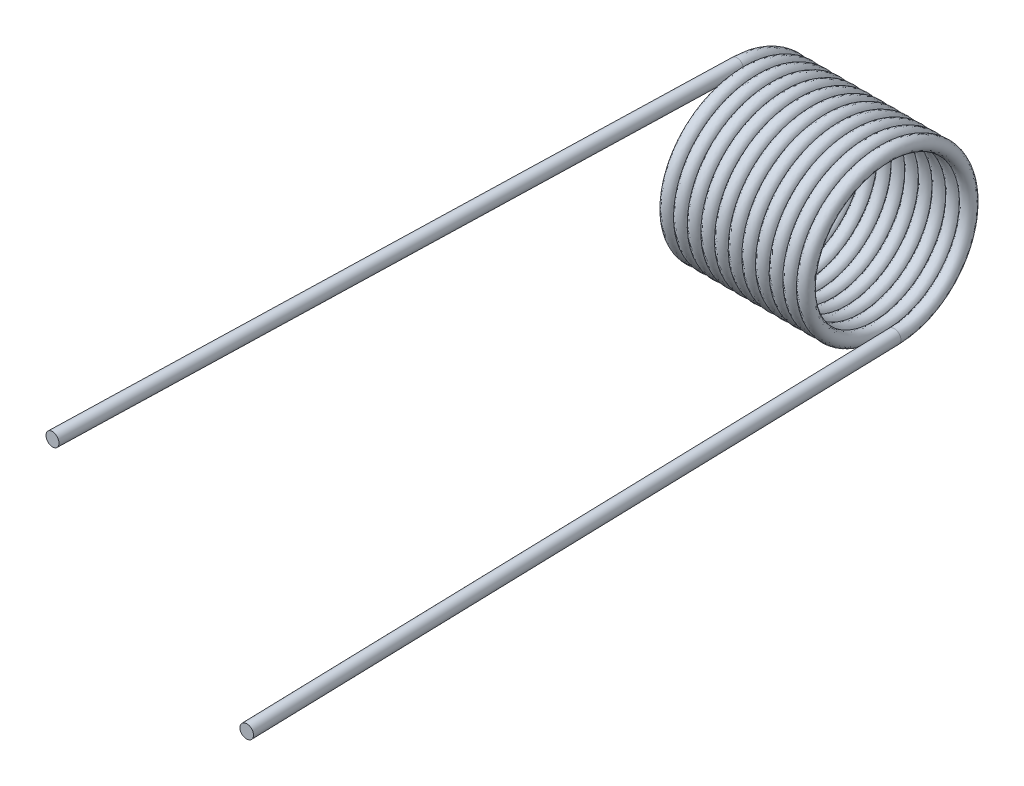
SolidWorks part; units mm, degrees
ref_plane "Front" through (0, 0, 0) normal (0, 0, 1) x (1, 0, 0)
ref_plane "Top" through (0, 0, 0) normal (0, 1, 0) x (1, 0, 0)
ref_plane "Right" through (0, 0, 0) normal (1, 0, 0) x (0, 0, -1)
sketch "Sketch1" plane through (0, 0, 0) normal (1, 0, 0) x (0, 0, -1)
  line L0 (0, 0) -> (0, -5.4356) construction
  line L1 (0, -5.4356) -> (0, -5.9436) construction
  line L2 (0, -5.9436) -> (0, -6.4516) construction
  circle A0 centre (0, 0) radius 5.4356 construction
  circle A1 centre (0, 0) radius 6.4516 construction
  circle A2 centre (0, 0) radius 5.9436
  circle A3 centre (0, -5.9436) radius 0.508 construction
  circle A4 centre (0, 0) radius 4.3561 construction
  dimension "Wire Dia" = 1.016
curve "Helix/Spiral1" pitch 1.0414 height 11.9761 radius 5.9436 left hand yes centre (0, 0, 0) axis (1, 0, 0) start towards (0, 1, 0)
ref_plane "Plane1" through (0, 5.9436, 0) normal (0.0279, 0, -0.9996) x (0.7745, 0.6323, 0.0216)
sketch "Sketch2" plane through (0, 5.9436, 0) normal (0.0279, 0, -0.9996) x (0.7745, 0.6323, 0.0216)
  circle A0 centre (0, 0) radius 0.508
  dimension "D1" = 1.016
sweep "Sweep1" add profiles "Sketch2" path "Helix/Spiral1"
sketch "Sketch3" plane through (0, 0, 0) normal (-0.0279, 0, 0.9996) x (-0.7745, -0.6323, -0.0216)
  circle A1 centre (-3.7579, -4.6048) radius 0.508
  circle A2 centre (-3.7579, -4.6048) radius 0.508
  dimension "D1" = 0
extrude "Extrude1" add sketch "Sketch3" along normal blind 50.8
sketch "Sketch4" plane through (0.0093, 0, 0.3337) normal (0.0279, 0, 0.9996) x (0.8176, -0.5754, -0.0228)
  circle A1 centre (13.2111, 2.0268) radius 0.508
  circle A2 centre (13.2111, 2.0268) radius 0.508
  dimension "D1" = 0
extrude "Extrude2" add sketch "Sketch4" along normal blind 50.8
sketch "Sketch5" plane through (0, 0, 0) normal (1, 0, 0) x (0, 0, -1)
  circle A0 centre (0, 0) radius 4.3561 construction
  circle A1 centre (0, 0) radius 4.3561
ref_axis "Axis1" through (-2.7151, 0, 0) along (1, 0, 0)
equation "\"D4@Helix/Spiral1\"=\"Wire Dia@Sketch1\"+.001"
equation "\"D1@Sketch2\"=\"Wire Dia@Sketch1\""
equation "\"D1@Extrude2\"=\"Leg Length@Extrude1\""
